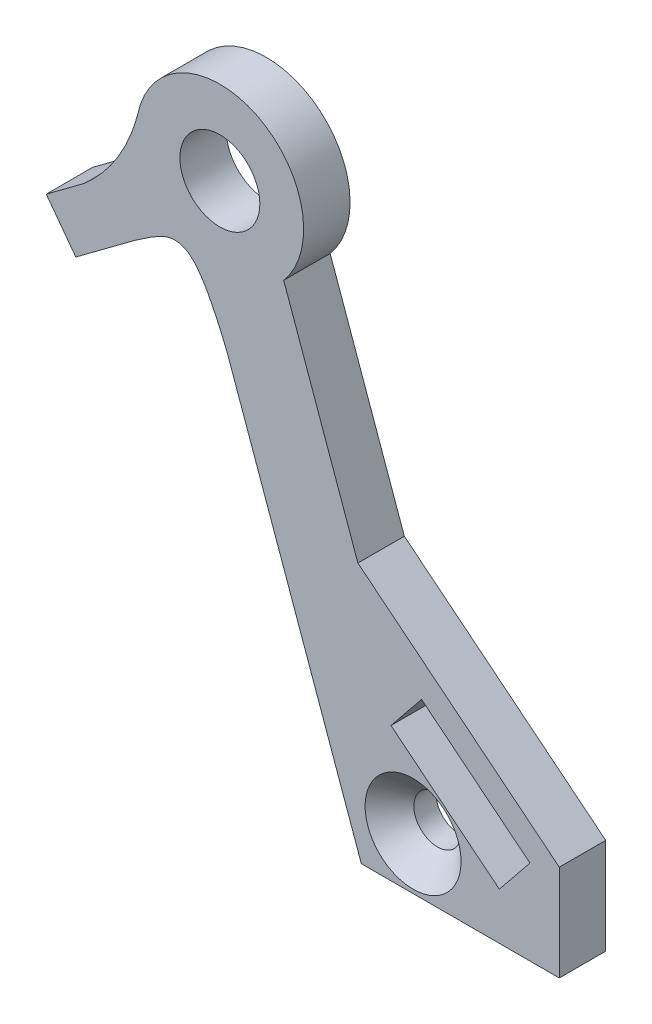
SolidWorks part; units mm, degrees
ref_plane "Front Plane" through (0, 0, 0) normal (0, 0, 1) x (1, 0, 0)
ref_plane "Top Plane" through (0, 0, 0) normal (0, 1, 0) x (1, 0, 0)
ref_plane "Right Plane" through (0, 0, 0) normal (1, 0, 0) x (0, 0, -1)
sketch "Sketch1" plane through (0, 0, 0) normal (0, 0, 1) x (1, 0, 0)
  line L0 (0, 10.5) -> (13, 0) construction
  line L1 (0, 0) -> (13, 0)
  line L2 (0, 0) -> (0, 10.5) construction
  line L3 (0, 10.5) -> (13, 10.5) construction
  line L4 (13, 0) -> (13, 10.5) construction
  line L5 (0, 0) -> (3.4, 0)
  line L6 (0, 0) -> (0, 3.4)
  line L7 (0, 3.4) -> (3.4, 3.4) construction
  line L8 (3.4, 0) -> (3.4, 3.4) construction
  line L9 (9.0068, 3.1288) -> (9.054, 3.1872) construction
  line L10 (9.0632, 3.0833) -> (1.945, 8.8326)
  line L11 (1.945, 8.8326) -> (3.9557, 11.322)
  line L12 (9.0632, 3.0833) -> (11.0738, 5.5728)
  line L13 (3.9557, 11.322) -> (11.0738, 5.5728)
  line L14 (0, 0) -> (-11.878, 33.265)
  line L15 (-11.878, 33.265) -> (-6.6984, 35.1146)
  line L16 (-6.6984, 35.1146) -> (-0.225, 16.9856)
  line L17 (-0.225, 16.9856) -> (13, 6.3039)
  line L18 (13, 0) -> (9.1103, 3.1417)
  line L19 (13, 6.3039) -> (13, 0)
  line L20 (0, 0) -> (0, 40.9886) construction
  line L21 (-9.2882, 34.1898) -> (-19.718, 26.4297) construction
  line L22 (-18.748, 25.126) -> (-20.688, 27.7335)
  line L23 (-20.688, 27.7335) -> (-14.4738, 32.357) construction
  line L24 (-18.748, 25.126) -> (-12.5338, 29.7495)
  line L25 (-20.688, 27.7335) -> (-18.2361, 29.5578)
  line L26 (-14.6691, 35.328) -> (-9.2882, 34.1898) construction
  circle A0 centre (3.4, 3.4) radius 1.5
  circle A1 centre (-9.2882, 34.1898) radius 2.625
  circle A3 centre (-9.2882, 34.1898) radius 5.5
  spline S0 degree 2 poles (-18.2361, 29.5578) (-15.5696, 31.8604) (-14.6691, 35.328) knots 0 0 0 1 1 1
  spline S1 degree 3 poles (-14.8727, 28.0094) (-13.3214, 29.0874) (-12.0342, 29.8701) (-10.3245, 28.4083) (-8.8034, 24.6542) knots 0 0 0 0 0.517104 1 1 1 1
  point P28 (-19.718, 26.4297)
  point P32 (0, 0)
  point P34 (9.0068, 3.1288)
  dimension "D5" = 3
  dimension "D6" = 5.25
  dimension "D7" = 11
  dimension "D26" = 6.892
  dimension "D1" = 13
  dimension "D2" = 10.5
  dimension "D3" = 3.4
  dimension "D4" = 3.4
  dimension "D8" = 51.072
  dimension "D9" = 6.3039
  dimension "D10" = 90
  dimension "D11" = 90
  dimension "D12" = 19.25
  dimension "D13" = 17
  dimension "D14" = 3.2
  dimension "D15" = 9.15
  dimension "D16" = 0.075
  dimension "D17" = 5
  dimension "D18" = 5.5
  dimension "D19" = 90
  dimension "D20" = 3.25
  dimension "D21" = 90
  dimension "D22" = 90
  dimension "D23" = 13
  dimension "D24" = 73
  dimension "D25" = 3.0562
  dimension "D27" = 31.593
extrude "Boss-Extrude1" add sketch "Sketch1" along normal blind 3.05 contours A3 S1 L14 L15 A1 L16 S0 | L14 A3 L16 L15 A1 | A3 L14 L1 L12 L10 L11 L13 L19 L17 L16 A0 | S0 L25 L22 L24 A3 | L24 S1 A3 | A3 S1 L14 region at (0.5621, 12.3676, 0) region at (-10.1685, 27.8055, 0) region at (-10.9043, 29.0949, 0) region at (-8.0964, 30.8521, 0) region at (-12.8691, 29.2752, 0) region at (-16.5541, 29.0906, 0)
hole_wizard "CSK for M3 Flat Head Machine Screw1" positions "Sketch2" profile "Sketch3" countersink size "M3" standard "ANSI Metric" end condition through all
sketch "Sketch2" plane through (0, 0, 3.05) normal (0, 0, 1) x (1, 0, 0)
  point P0 (3.4, 3.4)
sketch "Sketch3" plane through (3.4, 3.4, 3.05) normal (1, 0, 0) x (0, -1, 0)
  line L0 (0, 0) -> (0, 3.05)
  line L1 (0, 3.05) -> (1.55, 3.05)
  line L2 (1.55, 3.05) -> (1.55, 1.6)
  line L3 (1.55, 1.6) -> (3.15, 0)
  line L5 (3.15, 0) -> (0, 0)
  line L6 (-1.55, 1.6) -> (-3.15, 0) construction
  line L11 (0, -6.35) -> (0, 107.95) construction
  dimension "Thru Hole Dia." = 3.1
  dimension "Thru Hole Depth" = 3.05
  dimension "Near C'Sink Dia." = 6.3
  dimension "Near C'Sink Angle" = 90
